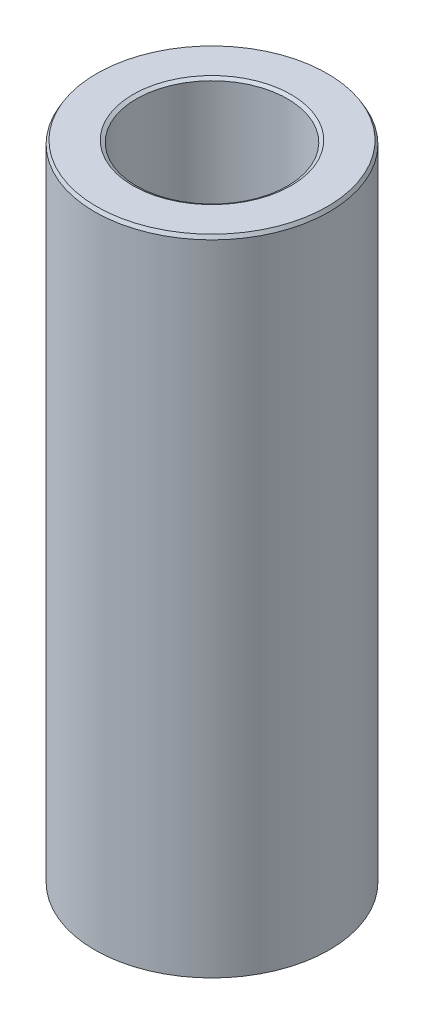
SolidWorks part; units mm, degrees
ref_plane "Front Plane" through (0, 0, 0) normal (0, 0, 1) x (1, 0, 0)
ref_plane "Top Plane" through (0, 0, 0) normal (0, 1, 0) x (1, 0, 0)
ref_plane "Right Plane" through (0, 0, 0) normal (1, 0, 0) x (0, 0, -1)
sketch "Sketch1" plane through (0, 0, 0) normal (0, 1, 0) x (1, 0, 0)
  circle A0 centre (0, 0) radius 40
  dimension "SLEEVE_OD" = 80
extrude "Boss-Extrude1" add sketch "Sketch1" along normal blind 219.8103
sketch "Sketch2" plane through (0, 0, 0) normal (0, 1, 0) x (1, 0, 0)
  circle A0 centre (0, 0) radius 25.7584
  dimension "BORE_D" = 51.5169
extrude "Cut-Extrude1" cut sketch "Sketch2" along normal through all
chamfer "Chamfer1" distance 1.1953 angle 30 4 edges at (0, 219.8103, 25.7584) (0, 0, 25.7584) (0, 0, 40) (0, 219.8103, 40) first distance on face at (0, 219.8103, 25.7584) first distance on face at (0, 0, 25.7584) first distance on face at (0, 219.8103, 40)
